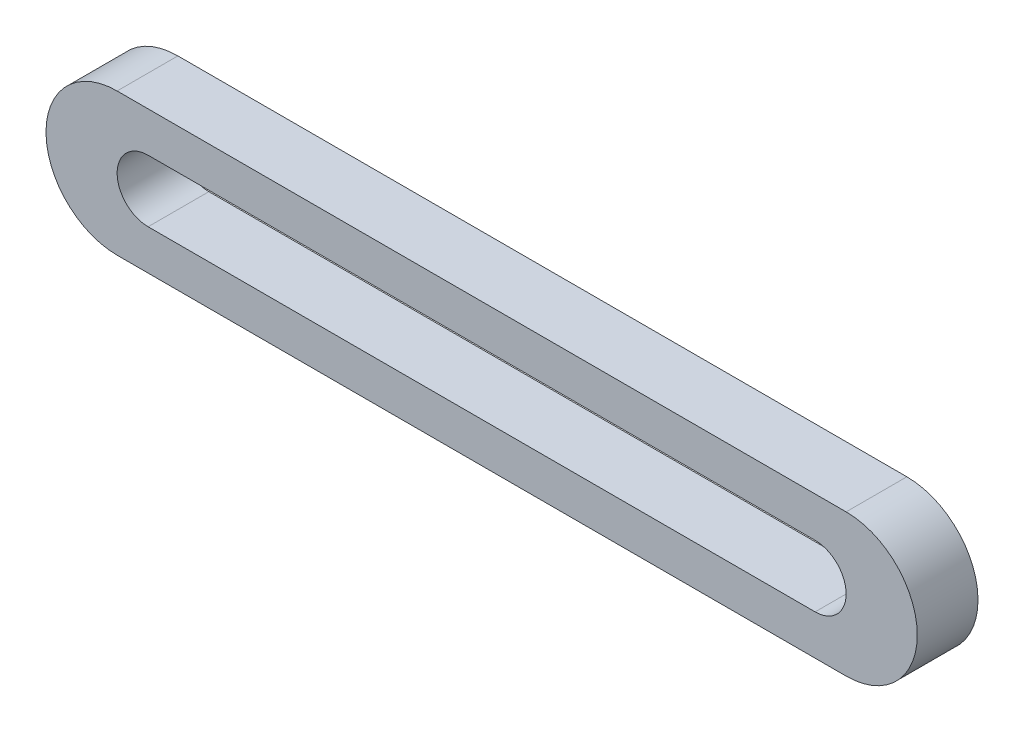
SolidWorks part; units mm, degrees
ref_plane "Front Plane" through (0, 0, 0) normal (0, 0, 1) x (1, 0, 0)
ref_plane "Top Plane" through (0, 0, 0) normal (0, 1, 0) x (1, 0, 0)
ref_plane "Right Plane" through (0, 0, 0) normal (1, 0, 0) x (0, 0, -1)
sketch "Sketch1" plane through (0, 0, 0) normal (0, 0, 1) x (1, 0, 0)
  line L3 (-82.55, 0) -> (-234.95, 0) construction
  line L4 (-82.55, -14.8683) -> (-234.95, -14.8683)
  line L5 (-82.55, 14.8683) -> (-234.95, 14.8683)
  arc A2 (-82.55, -14.8683) -> (-82.55, 14.8683) centre (-82.55, 0) ccw
  arc A3 (-234.95, 14.8683) -> (-234.95, -14.8683) centre (-234.95, 0) ccw
  point P12 (-158.75, 0)
  dimension "D3" = 152.4
extrude "Boss-Extrude2" add sketch "Sketch1" along normal blind 12.7
sketch "Sketch2" plane through (0, 0, 0) normal (0, 0, -1) x (-1, 0, 0)
  line L0 (67.6817, 0) -> (249.8183, 0) construction
  line L1 (158.75, 14.8683) -> (158.75, -14.8683) construction
  line L2 (82.55, 14.8683) -> (234.95, 14.8683) construction
  line L3 (234.95, -14.8683) -> (82.55, -14.8683) construction
  line L4 (228.473, 0) -> (89.027, 0) construction
  line L5 (228.473, -6.477) -> (89.027, -6.477)
  line L6 (228.473, 6.477) -> (89.027, 6.477)
  arc A0 (82.55, 14.8683) -> (82.55, -14.8683) centre (82.55, 0) ccw construction
  arc A1 (234.95, -14.8683) -> (234.95, 14.8683) centre (234.95, 0) ccw construction
  arc A2 (228.473, -6.477) -> (228.473, 6.477) centre (228.473, 0) ccw
  arc A3 (89.027, 6.477) -> (89.027, -6.477) centre (89.027, 0) ccw
  point P16 (158.75, 0)
  point P21 (82.55, 0)
  point P22 (234.95, 0)
  dimension "D2" = 152.4
  dimension "D1" = 12.954
extrude "Cut-Extrude1" cut sketch "Sketch2" against normal blind 38.862
